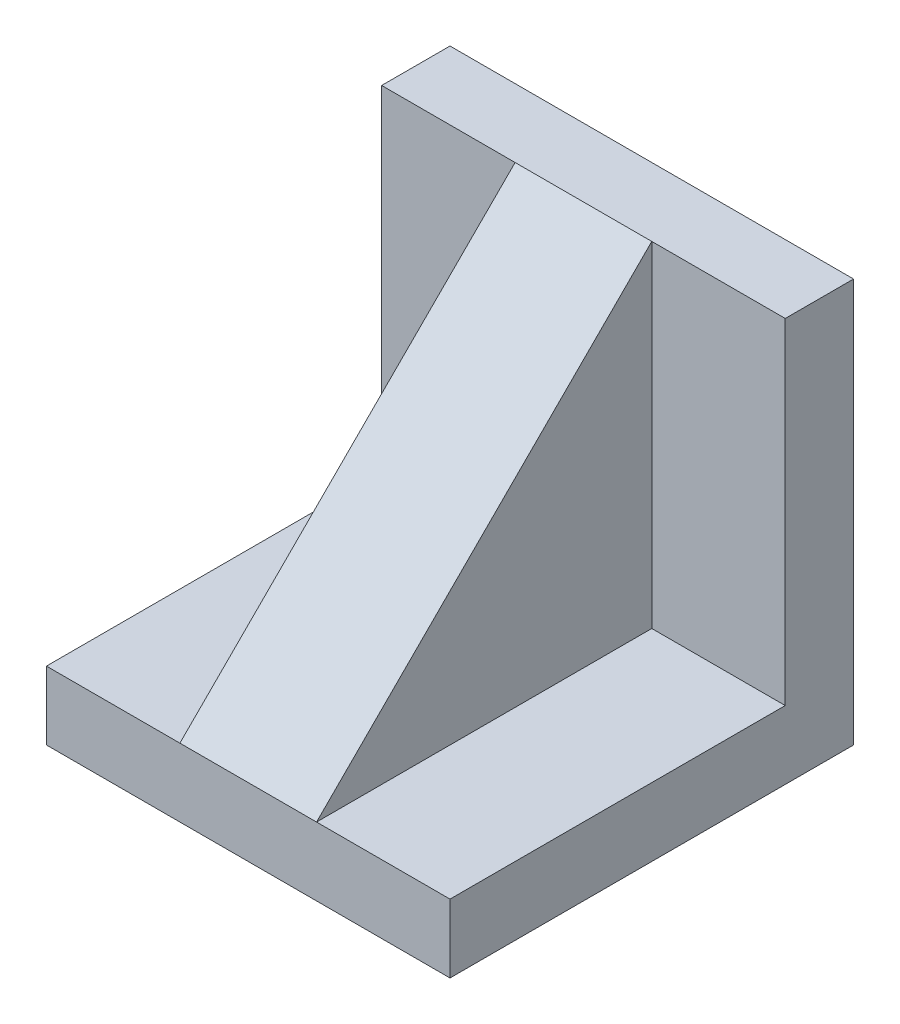
SolidWorks part; units mm, degrees
ref_plane "Front Plane" through (0, 0, 0) normal (1, 0, 0) x (0, 1, 0)
ref_plane "Top Plane" through (0, 0, 0) normal (0, 0, 1) x (0, 1, 0)
ref_plane "Right Plane" through (0, 0, 0) normal (0, 1, 0) x (-1, 0, 0)
sketch "Sketch1" plane through (0, 0, 0) normal (1, 0, 0) x (0, 1, 0)
  line L0 (0, 0) -> (0, 150)
  line L1 (0, 150) -> (25.4, 150)
  line L2 (25.4, 150) -> (25.4, 25.4)
  line L3 (25.4, 25.4) -> (150, 25.4)
  line L4 (150, 25.4) -> (150, 0)
  line L5 (150, 0) -> (0, 0)
  dimension "D1" = 25.4
  dimension "D2" = 150
  dimension "D3" = 150
  dimension "D4" = 25.4
extrude "Boss-Extrude1" add sketch "Sketch1" along normal blind 75 and the other way blind 75 contours L2 L3 L4 L5 L0 L1
sketch "Sketch3" plane through (0, 0, 0) normal (1, 0, 0) x (0, 1, 0)
  line L0 (0, 150) -> (25.4, 150)
  line L1 (25.4, 150) -> (150, 25.4)
  line L2 (150, 25.4) -> (150, 0)
  line L3 (150, 0) -> (0, 0)
  line L4 (0, 0) -> (0, 150)
  line L6 (150, 25.4) -> (150, 0) construction
  point P2 (0, 150)
  point P6 (150, 0)
  point P10 (150, 25.4)
  point P11 (25.4, 150)
extrude "Boss-Extrude2" add sketch "Sketch3" along normal blind 25.4 and the other way blind 25.4
